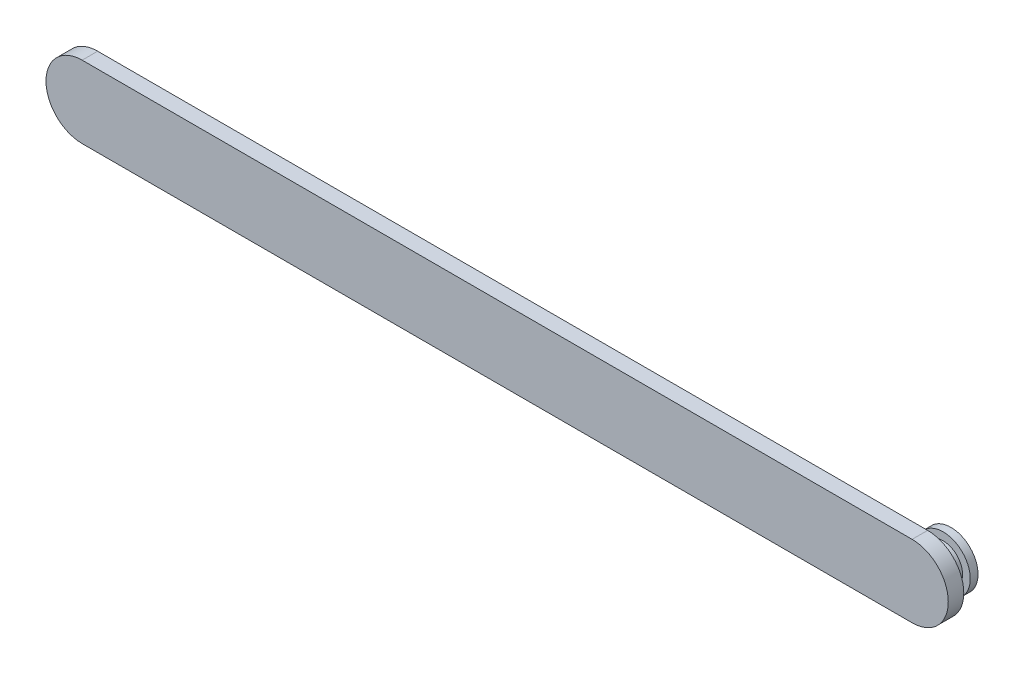
SolidWorks part; units mm, degrees
ref_plane "Front Plane" through (0, 0, 0) normal (0, 0, 1) x (1, 0, 0)
ref_plane "Top Plane" through (0, 0, 0) normal (0, 1, 0) x (1, 0, 0)
ref_plane "Right Plane" through (0, 0, 0) normal (1, 0, 0) x (0, 0, -1)
sketch "Sketch1" plane through (0, 0, 0) normal (0, 0, 1) x (1, 0, 0)
  line L0 (0, 5.9182) -> (135.89, 5.9182)
  line L1 (135.89, -5.9182) -> (0, -5.9182)
  arc A0 (0, 5.9182) -> (0, -5.9182) centre (0, 0) ccw
  arc A1 (135.89, 5.9182) -> (135.89, -5.9182) centre (135.89, 0) cw
  point P7 (0, 0)
  dimension "D1" = 11.8364
  dimension "D2" = 135.89
extrude "Boss-Extrude1" add sketch "Sketch1" along normal blind 2.54
sketch "Sketch2" plane through (0, 0, 0) normal (0, 0, -1) x (-1, 0, 0)
  circle A0 centre (-135.89, 0) radius 3.175
  dimension "D1" = 6.35
extrude "Boss-Extrude2" add sketch "Sketch2" along normal blind 2.54
sketch "Sketch3" plane through (0, 0, -2.54) normal (0, 0, -1) x (-1, 0, 0)
  circle A0 centre (-135.89, 0) radius 4.445
  circle A1 centre (-135.89, 0) radius 3.175 construction
  dimension "D1" = 8.89
extrude "Boss-Extrude3" add sketch "Sketch3" along normal blind 1.27
